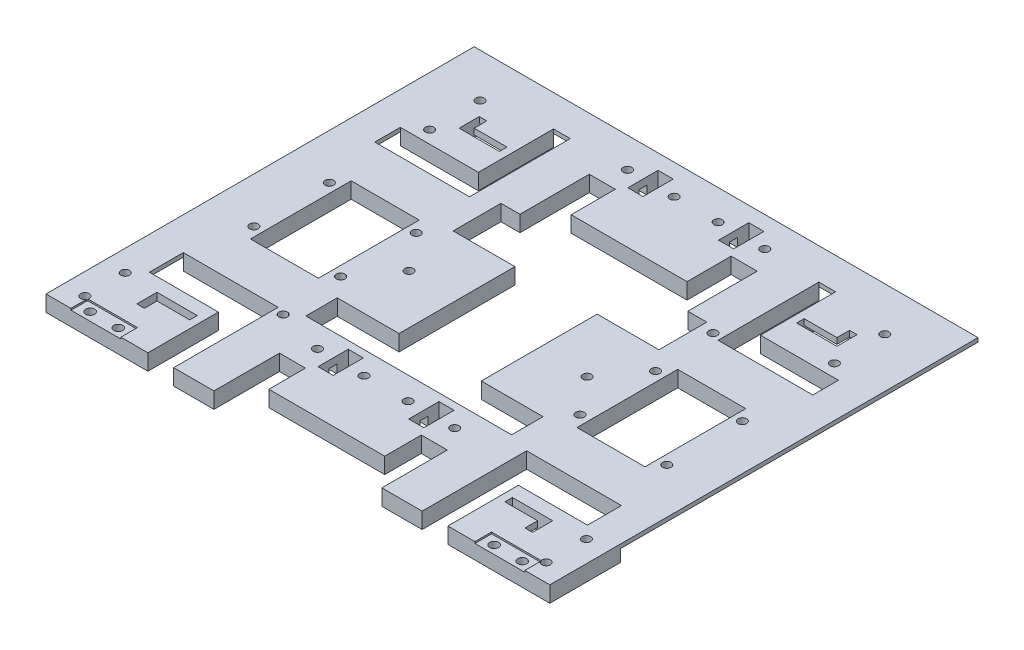
SolidWorks part; units mm, degrees
material "AISI 4130 Steel, normalized at 870C"
ref_plane "Front Plane" through (0, 0, 0) normal (0, 0, 1) x (1, 0, 0)
ref_plane "Top Plane" through (0, 0, 0) normal (0, 1, 0) x (1, 0, 0)
ref_plane "Right Plane" through (0, 0, 0) normal (1, 0, 0) x (0, 0, -1)
sketch "Sketch1" plane through (0, 0, 0) normal (0, 1, 0) x (1, 0, 0)
  line L1 (-100, -85) -> (100, -85)
  line L2 (-100, -85) -> (-100, 85)
  line L3 (-100, 85) -> (100, 85)
  line L4 (100, -85) -> (100, 85)
  line L5 (-100, -85) -> (100, 85) construction
  line L6 (-100, 85) -> (100, -85) construction
  point P0 (0, 0)
  dimension "D1" = 200
  dimension "D2" = 170
extrude "1/4\" Steel Plate" add sketch "Sketch1" along normal blind 6.35
ref_plane "Midplane" through (0, 0, 0) normal (-1, 0, 0) x (0, 0, 1)
sketch "Sketch2" plane through (0, 6.35, 0) normal (0, 1, 0) x (1, 0, 0)
  line L0 (-100, -85) -> (100, -85) construction
  line L1 (-90.094, -85) -> (-70.282, -85)
  line L2 (-90.094, -85) -> (-90.094, -78.396)
  line L3 (-90.094, -78.396) -> (-70.282, -78.396)
  line L4 (-70.282, -85) -> (-70.282, -78.396)
  line L5 (-100, 85) -> (-100, -85) construction
  dimension "D1" = 9.906
  dimension "D2" = 6.604
  dimension "D3" = 19.812
extrude "BladeHingeCut" cut sketch "Sketch2" against normal blind 0.635
hole_wizard "BladeHingeHole" positions "3DSketch2" profile "Sketch4" hole size "#8" standard "ANSI Inch" end condition through all
sketch3d "3DSketch2"
  line L0 (-90.094, 5.715, 85) -> (-70.282, 5.715, 85) construction
  line L10 (-80.188, 5.715, 78.396) -> (-80.188, 5.715, 85) construction
  line L11 (-70.282, 5.715, 78.396) -> (-90.094, 5.715, 78.396) construction
  point P0 (-74.6, 5.715, 81.698)
  point P2 (-85.776, 5.715, 81.698)
  dimension "D1" = 3.302
  dimension "D2" = 3.302
  dimension "D3" = 11.176
  dimension "D4" = 5.588
sketch "Sketch4" plane through (-74.6, 5.715, 81.698) normal (1, 0, 0) x (0, 0, 1)
  line L0 (0, 0) -> (0, 5.715)
  line L1 (0, 5.715) -> (1.778, 5.715)
  line L2 (1.778, 5.715) -> (1.778, 0)
  line L5 (1.778, 0) -> (0, 0)
  line L11 (0, -6.35) -> (0, 107.95) construction
  dimension "Thru Hole Dia." = 3.556
  dimension "Thru Hole Depth" = 5.715
sketch "Sketch5" plane through (0, 0, 0) normal (0, -1, 0) x (1, 0, 0)
  line L1 (-88.301, 79.173) -> (-83.251, 79.173)
  line L2 (-88.301, 79.173) -> (-88.301, 84.223)
  line L3 (-88.301, 84.223) -> (-83.251, 84.223)
  line L4 (-83.251, 79.173) -> (-83.251, 84.223)
  line L5 (-88.301, 79.173) -> (-83.251, 84.223) construction
  line L6 (-88.301, 84.223) -> (-83.251, 79.173) construction
  line L7 (-72.075, 79.173) -> (-77.125, 79.173)
  line L8 (-72.075, 79.173) -> (-72.075, 84.223)
  line L9 (-72.075, 84.223) -> (-77.125, 84.223)
  line L10 (-77.125, 79.173) -> (-77.125, 84.223)
  line L11 (-72.075, 79.173) -> (-77.125, 84.223) construction
  line L12 (-72.075, 84.223) -> (-77.125, 79.173) construction
  point P0 (-85.776, 81.698)
  point P6 (-74.6, 81.698)
  dimension "D1" = 5.05
  dimension "D2" = 5.05
  dimension "D3" = 5.05
  dimension "D4" = 5.05
extrude "BladeNutCut" cut sketch "Sketch5" against normal blind 2
mirror "BladeHingeMirror" about plane through (0, 0, 0) normal (-1, 0, 0) of "BladeNutCut", "BladeHingeHole", "BladeHingeCut"
sketch "Sketch6" plane through (0, 0, 0) normal (0, -1, 0) x (-1, 0, 0)
  line L0 (77.3259, -27.4233) -> (77.3259, 16.3767) construction
  line L1 (78.3259, 14.4767) -> (51.3259, 14.4767)
  line L2 (78.3259, 14.4767) -> (78.3259, -25.5233)
  line L3 (78.3259, -25.5233) -> (51.3259, -25.5233)
  line L4 (51.3259, 14.4767) -> (51.3259, -25.5233)
  line L5 (57.3259, 16.3767) -> (57.3259, -27.4233) construction
  point P6 (78.3259, -5.5233)
  dimension "D1" = 1
  dimension "D2" = 20
  dimension "D3" = 6
  dimension "D4" = 20
extrude "Cut-Extrude1" cut sketch "Sketch6" against normal up to surface (6.35 mm away) up to face at (0, 6.35, 54.4653)
sketch "Sketch7" plane through (0, 0, 0) normal (0, -1, 0) x (-1, 0, 0)
  line L0 (51.3259, -25.5233) -> (78.3259, -25.5233) construction
  line L1 (79.3259, -30.5233) -> (49.3259, -30.5233)
  line L2 (79.3259, -30.5233) -> (79.3259, -40.5233)
  line L3 (79.3259, -40.5233) -> (49.3259, -40.5233)
  line L4 (49.3259, -30.5233) -> (49.3259, -40.5233)
  line L5 (80.3259, 19.4767) -> (50.3259, 19.4767)
  line L6 (80.3259, 19.4767) -> (80.3259, 29.4767)
  line L7 (80.3259, 29.4767) -> (50.3259, 29.4767)
  line L8 (50.3259, 19.4767) -> (50.3259, 29.4767)
  line L9 (29.3259, -25.5233) -> (19.3259, -25.5233)
  line L10 (29.3259, -25.5233) -> (29.3259, 14.4767)
  line L11 (29.3259, 14.4767) -> (19.3259, 14.4767)
  line L12 (19.3259, -25.5233) -> (19.3259, 14.4767)
  line L17 (78.3259, -25.5233) -> (78.3259, 14.4767) construction
  line L18 (78.3259, 14.4767) -> (51.3259, 14.4767) construction
  line L19 (51.3259, 14.4767) -> (51.3259, -25.5233) construction
  line L29 (46.3259, -80.5233) -> (36.3259, -80.5233)
  line L30 (46.3259, -80.5233) -> (46.3259, -50.5233)
  line L31 (46.3259, -50.5233) -> (36.3259, -50.5233)
  line L32 (36.3259, -80.5233) -> (36.3259, -50.5233)
  line L33 (20, -70.5233) -> (-20, -70.5233)
  line L34 (20, -70.5233) -> (20, -60.5233)
  line L35 (20, -60.5233) -> (-20, -60.5233)
  line L36 (-20, -70.5233) -> (-20, -60.5233)
  line L37 (-100, 85) -> (100, 85) construction
  line L38 (36.3259, 39.4767) -> (46.3259, 39.4767)
  line L39 (36.3259, 39.4767) -> (36.3259, 69.4767)
  line L40 (36.3259, 69.4767) -> (46.3259, 69.4767)
  line L41 (46.3259, 39.4767) -> (46.3259, 69.4767)
  line L42 (20, 49.4767) -> (-20, 49.4767)
  line L43 (20, 49.4767) -> (20, 59.4767)
  line L44 (20, 59.4767) -> (-20, 59.4767)
  line L45 (-20, 49.4767) -> (-20, 59.4767)
  point P18 (0, 49.4767)
  point P55 (20, 54.4767)
  point P56 (36.3259, 54.4767)
  point P57 (20, -65.5233)
  point P58 (36.3259, -65.5233)
  point P60 (0, 85)
  dimension "D1" = 5
  dimension "D2" = 30
  dimension "D3" = 10
  dimension "D4" = 1
  dimension "D5" = 5
  dimension "D6" = 1
  dimension "D7" = 10
  dimension "D8" = 30
  dimension "D9" = 40
  dimension "D10" = 10
  dimension "D11" = 22
  dimension "D14" = 10
  dimension "D17" = 5
  dimension "D18" = 40
  dimension "D19" = 10
  dimension "D20" = 30
  dimension "D21" = 25
  dimension "D22" = 10
  dimension "D23" = 30
  dimension "D24" = 25
  dimension "D25" = 10
  dimension "D26" = 40
other "AlignGroup1"
extrude "Cut-Extrude2" cut sketch "Sketch7" against normal blind 5 contours L30 L29 L32 L31 | L34 L33 L36 L35 | L10 L9 L12 L11 | L2 L1 L4 L3 | L6 L5 L8 L7 | L39 L38 L41 L40 | L43 L42 L45 L44
sketch "Sketch8" plane through (0, 6.35, 0) normal (0, 1, 0) x (1, 0, 0)
  line L0 (-83.5459, -55) -> (-83.5459, -85) construction
  line L1 (-78.5459, -62.396) -> (-62.5459, -62.396)
  line L2 (-78.5459, -62.396) -> (-78.5459, -73.396)
  line L3 (-78.5459, -73.396) -> (-62.5459, -73.396)
  line L4 (-62.5459, -62.396) -> (-62.5459, -73.396)
  line L5 (-70.282, -78.396) -> (-90.094, -78.396) construction
  dimension "D1" = 11
  dimension "D2" = 16
  dimension "D3" = 5
  dimension "D4" = 5
extrude "Cut-Extrude3" cut sketch "Sketch8" along normal blind 4 from surface starting at face at (0, 0, -54.4767)
sketch "Sketch9" plane through (0, 4, 0) normal (0, -1, 0) x (1, 0, 0)
  line L0 (-78.5459, 62.396) -> (-62.5459, 62.396)
  line L9 (-78.5459, 62.396) -> (-78.5459, 70.396)
  line L10 (-78.5459, 73.396) -> (-78.5459, 62.396) construction
  line L11 (-78.5459, 70.396) -> (-75.5459, 70.396)
  line L12 (-75.5459, 70.396) -> (-75.5459, 65.396)
  line L13 (-75.5459, 65.396) -> (-62.5459, 65.396)
  line L14 (-62.5459, 62.396) -> (-62.5459, 73.396) construction
  line L15 (-62.5459, 65.396) -> (-62.5459, 62.396)
  dimension "D1" = 8
  dimension "D2" = 3
  dimension "D3" = 3
extrude "Cut-Extrude4" cut sketch "Sketch9" against normal up to surface (2.35 mm away) contours L13 L15 L0 L9 L11 L12 up to face at (-64.8259, 6.35, 5.5233)
sketch "Sketch10" plane through (0, 0, 0) normal (0, -1, 0) x (-1, 0, 0)
  line L1 (75, 65) -> (59, 65)
  line L2 (75, 65) -> (75, 54)
  line L3 (75, 54) -> (59, 54)
  line L4 (59, 65) -> (59, 54)
  line L6 (100, 85) -> (100, -85) construction
  line L7 (-100, 85) -> (100, 85) construction
  dimension "D1" = 11
  dimension "D2" = 16
  dimension "D3" = 25
  dimension "D4" = 20
extrude "Cut-Extrude5" cut sketch "Sketch10" against normal blind 4
sketch "Sketch11" plane through (0, 4, 0) normal (0, -1, 0) x (1, 0, 0)
  line L0 (-59, -54) -> (-75, -54)
  line L1 (-75, -54) -> (-75, -62)
  line L2 (-75, -54) -> (-75, -65) construction
  line L3 (-75, -62) -> (-72, -62)
  line L4 (-72, -62) -> (-72, -57)
  line L5 (-72, -57) -> (-59, -57)
  line L6 (-59, -65) -> (-59, -54) construction
  line L7 (-59, -57) -> (-59, -54)
  dimension "D1" = 3
  dimension "D2" = 3
  dimension "D3" = 8
extrude "Cut-Extrude6" cut sketch "Sketch11" against normal up to next
mirror "Mirror2" about plane through (0, 0, 0) normal (-1, 0, 0) of "Cut-Extrude6", "Cut-Extrude5", "Cut-Extrude4", "Cut-Extrude3", "Cut-Extrude2", "Cut-Extrude1"
hole_wizard "CSK for M3 Flat Head Machine Screw1" positions "Sketch12" profile "Sketch13" countersink size "M3" standard "ANSI Metric"
sketch "Sketch12" plane through (0, 0, 0) normal (0, -1, 0) x (-1, 0, 0)
  point P0 (-91.5503, -78)
  point P2 (-91.5503, -62)
  point P4 (-80.3371, 47.6378)
  point P7 (-80.3371, 67.6378)
  point P10 (-35.8509, -6.0466)
  point P13 (-45.8509, 33.9534)
  point P16 (35.8509, -5)
  point P19 (45.8509, -45)
  point P22 (91.5459, -62)
  point P25 (91.5459, -78)
  point P28 (80.3371, 47.6378)
  point P31 (80.3371, 67.6378)
  point P39 (-81.9659, -20.5233)
  point P42 (-81.9659, 9.4767)
  point P45 (-47.5109, -20.5233)
  point P48 (-47.5109, 9.4767)
  point P51 (47.5109, -20.5233)
  point P54 (81.9659, -20.5233)
  point P57 (81.9659, 9.4767)
  point P60 (47.5109, 9.4767)
sketch "Sketch13" plane through (91.5503, 0, 78) normal (1, 0, 0) x (0, 0, -1)
  line L0 (0, 0) -> (0, 14)
  line L1 (0, 14) -> (1.7, 14)
  line L2 (1.7, 14) -> (1.7, 1.45)
  line L3 (1.7, 1.45) -> (3.15, 0)
  line L5 (3.15, 0) -> (0, 0)
  line L6 (-1.7, 1.45) -> (-3.15, 0) construction
  line L10 (0, 14) -> (-1.7, 14) construction
  line L11 (0, -6.35) -> (0, 107.95) construction
  dimension "Hole Dia." = 3.4
  dimension "Hole Depth" = 14
  dimension "Near C'Sink Dia." = 6.3
  dimension "Near C'Sink Angle" = 90
  dimension "Drill Angle" = 180
sketch "Sketch14" plane through (0, 0, 0) normal (0, -1, 0) x (1, 0, 0)
  line L0 (0, -7.6262) -> (0, -14.6112) construction
  line L1 (21, 56) -> (15, 56)
  line L2 (21, 56) -> (21, 44)
  line L3 (21, 44) -> (15, 44)
  line L4 (15, 56) -> (15, 44)
  line L6 (-100, 85) -> (100, 85) construction
  point P6 (15, 50)
  dimension "D1" = 6
  dimension "D2" = 12
  dimension "D3" = 15
  dimension "D4" = 35
extrude "Cut-Extrude7" cut sketch "Sketch14" against normal blind 10
sketch "Sketch15" plane through (0, 0, 0) normal (0, -1, 0) x (1, 0, 0)
  line L1 (10.75, 48.4) -> (25.25, 48.4)
  line L2 (10.75, 48.4) -> (10.75, 51.6)
  line L3 (10.75, 51.6) -> (25.25, 51.6)
  line L4 (25.25, 48.4) -> (25.25, 51.6)
  line L5 (15, 56) -> (15, 44) construction
  line L6 (15, 44) -> (21, 44) construction
  point P6 (18, 44)
  point P9 (15, 50)
  point P10 (10.75, 50)
  point P11 (18, 48.4)
  dimension "D2" = 14.5
  dimension "D3" = 3.2
extrude "Cut-Extrude8" cut sketch "Sketch15" against normal blind 3.5
sketch "Sketch16" plane through (0, 0, 0) normal (0, -1, 0) x (1, 0, 0)
  line L0 (15, 44) -> (21, 44) construction
  line L1 (15, -79) -> (21, -79)
  line L2 (15, -79) -> (15, -67)
  line L3 (15, -67) -> (21, -67)
  line L4 (21, -79) -> (21, -67)
  line L5 (100, -85) -> (-100, -85) construction
  point P6 (18, 44)
  point P7 (18, -67)
  point P8 (15, -73)
  dimension "D1" = 12
  dimension "D2" = 6
  dimension "D3" = 12
extrude "Cut-Extrude9" cut sketch "Sketch16" against normal through all
sketch "Sketch17" plane through (0, 0, 0) normal (0, -1, 0) x (1, 0, 0)
  line L1 (10.75, -74.6) -> (25.25, -74.6)
  line L2 (10.75, -74.6) -> (10.75, -71.4)
  line L3 (10.75, -71.4) -> (25.25, -71.4)
  line L4 (25.25, -74.6) -> (25.25, -71.4)
  line L8 (21, -67) -> (15, -67) construction
  line L9 (15, -67) -> (15, -79) construction
  point P6 (15, -73)
  point P7 (10.75, -73)
  point P14 (18, -67)
  point P15 (18, -71.4)
  dimension "D1" = 14.5
  dimension "D2" = 3.2
extrude "Cut-Extrude10" cut sketch "Sketch17" against normal blind 3.5
hole_wizard "CSK for M3 Flat Head Machine Screw2" positions "Sketch18" profile "Sketch19" countersink size "M3" standard "ANSI Metric"
sketch "Sketch18" plane through (0, 0, 0) normal (0, -1, 0) x (-1, 0, 0)
  line L2 (-21, 74.6) -> (-25.25, 74.6) construction
  line L4 (-10.75, 74.6) -> (-15, 74.6) construction
  line L5 (-25.25, 74.6) -> (-25.25, 71.4) construction
  line L6 (-10.75, 71.4) -> (-10.75, 74.6) construction
  line L7 (-25.25, -48.4) -> (-25.25, -51.6) construction
  point P0 (-8.75, -50)
  point P4 (-27.25, -50)
  point P6 (-8.75, 73.1)
  point P8 (-27.25, 73.1)
  point P27 (0, 0)
  point P30 (-25.25, -50)
  dimension "D1" = 1.5
  dimension "D2" = 1.5
  dimension "D3" = 2
  dimension "D4" = 2
sketch "Sketch19" plane through (8.75, 0, 50) normal (1, 0, 0) x (0, 0, -1)
  line L0 (0, 0) -> (0, 11.0215)
  line L1 (0, 11.0215) -> (1.7, 10)
  line L2 (1.7, 10) -> (1.7, 1.45)
  line L3 (1.7, 1.45) -> (3.15, 0)
  line L5 (3.15, 0) -> (0, 0)
  line L6 (-1.7, 1.45) -> (-3.15, 0) construction
  line L10 (0, 11.0215) -> (-1.7, 10) construction
  line L11 (0, -6.35) -> (0, 107.95) construction
  dimension "Hole Dia." = 3.4
  dimension "Hole Depth" = 10
  dimension "Near C'Sink Dia." = 6.3
  dimension "Near C'Sink Angle" = 90
  dimension "Drill Angle" = 118
mirror "Mirror3" about plane through (0, 0, 0) normal (-1, 0, 0) of "Cut-Extrude7", "Cut-Extrude8", "Cut-Extrude9", "Cut-Extrude10", "CSK for M3 Flat Head Machine Screw2"
sketch "Sketch20" plane through (0, 0, 0) normal (0, -1, 0) x (1, 0, 0)
  line L0 (-100, 85) -> (100, 85) construction
  line L1 (-59.5459, 85) -> (-49.3259, 85)
  line L2 (-59.5459, 85) -> (-59.5459, 57)
  line L3 (-50.8509, 50) -> (-49.3259, 50)
  line L4 (-49.3259, 85) -> (-49.3259, 50)
  line L5 (-100, -85) -> (-100, 85) construction
  line L6 (-100, 57) -> (-59.5459, 57)
  line L7 (-100, 57) -> (-100, 45.2891)
  line L8 (-86.9659, 43.5233) -> (-50.8509, 43.5233)
  line L9 (-50.8509, 50) -> (-50.8509, 43.5233)
  line L10 (100, -85) -> (-100, -85) construction
  line L12 (-86.9659, 43.5233) -> (-86.9659, -32.4767)
  line L13 (-89.1269, -85) -> (-100, -85)
  line L14 (-100, 45.2891) -> (-100, -85)
  line L15 (-86.9659, -32.4767) -> (-49.3259, -32.4767)
  line L17 (-86.9659, -42.6378) -> (-56, -42.6378)
  line L18 (-49.3259, -35.2903) -> (-49.3259, -42.3731)
  line L19 (-86.9659, -72.4767) -> (-56, -72.4767)
  line L21 (-89.1269, -85) -> (-46.8803, -85)
  line L23 (-86.9659, -42.6378) -> (-86.9659, -72.4767)
  line L25 (-56, -42.6378) -> (-56, -72.4767)
  line L27 (-49.3259, -42.3731) -> (-49.3259, -72.4767)
  line L28 (-40.8509, -17.4767) -> (-20.1564, -17.4767)
  line L29 (-40.8509, -17.4767) -> (-40.8509, -31.3828)
  line L30 (-40.8509, -36.4767) -> (-33.3259, -36.4767)
  line L33 (-33.3259, -36.4767) -> (-33.3259, -64)
  line L34 (-33.3259, -64) -> (-23, -64)
  line L35 (-23, -46.4767) -> (-23, -64)
  line L36 (-44.7194, -72.4767) -> (-32.25, -72.4767)
  line L38 (-46.8803, -85) -> (-32.25, -85)
  line L39 (-32.25, -72.4767) -> (-32.25, -85)
  line L40 (-40.8509, 41) -> (-20.1564, 41)
  line L41 (-40.8509, 41) -> (-40.8509, 28.5233)
  line L42 (-40.8509, 28.5233) -> (-20.1564, 28.5233)
  line L44 (-33.3259, 85) -> (-23, 85)
  line L45 (-33.3259, 85) -> (-33.3259, 59)
  line L46 (-33.3259, 59) -> (-23, 59)
  line L47 (-23, 85) -> (-23, 59)
  line L48 (0, 41) -> (-15.9718, 41)
  line L49 (0, 41) -> (0, -46.4767)
  line L50 (0, -46.4767) -> (-15.9718, -46.4767)
  line L51 (-16.3259, 28.5233) -> (-16.3259, -17.4767)
  line L52 (-49.3259, -72.4767) -> (-44.7194, -72.4767)
  line L54 (-40.8509, -31.3828) -> (-40.8509, -36.4767)
  line L55 (-20.1564, 41) -> (-15.9718, 41)
  line L57 (-20.1564, 28.5233) -> (-16.3259, 28.5233)
  line L59 (-20.1564, -17.4767) -> (-16.3259, -17.4767)
  line L61 (-20.1564, -46.4767) -> (-15.9718, -46.4767)
  line L65 (-23, -46.4767) -> (-20.1564, -46.4767)
  line L71 (-49.3259, -32.4767) -> (-49.3259, -35.2903)
  line L72 (-46.3259, -39.4767) -> (-46.3259, -69.4767) construction
  line L73 (-80.3259, -29.4767) -> (-50.3259, -29.4767) construction
  line L74 (-79.3259, 40.5233) -> (-49.3259, 40.5233) construction
  line L75 (-46.3259, 80.5233) -> (-46.3259, 50.5233) construction
  line L76 (-62.5459, 65.396) -> (-62.5459, 73.396) construction
  line L77 (-36.3259, 80.5233) -> (-36.3259, 50.5233) construction
  line L78 (-20, 70.5233) -> (-20, 60.5233) construction
  line L79 (-21, 56) -> (-15, 56) construction
  line L80 (-15, 44) -> (-21, 44) construction
  line L81 (-29.3259, 25.5233) -> (-19.3259, 25.5233) construction
  line L82 (-19.3259, 25.5233) -> (-19.3259, -14.4767) construction
  line L83 (-29.3259, -14.4767) -> (-19.3259, -14.4767) construction
  line L84 (-20, -49.4767) -> (20, -49.4767) construction
  line L85 (-20, -49.4767) -> (-20, -59.4767) construction
  line L86 (-36.3259, -39.4767) -> (-36.3259, -69.4767) construction
  line L87 (-36.3259, -39.4767) -> (-46.3259, -39.4767) construction
  line L88 (-21, -67) -> (-15, -67) construction
  line L89 (-36.3259, -69.4767) -> (-46.3259, -69.4767) construction
  line L90 (-59, -65) -> (-59, -54) construction
  line L91 (0, 3.4925) -> (0, -3.4925) construction
  line L92 (-20, 70.5233) -> (20, 70.5233) construction
  line L93 (-23, 85) -> (0, 85)
  line L94 (-23, 85) -> (-23, 73.5233)
  line L95 (-23, 73.5233) -> (0, 73.5233)
  line L96 (0, 85) -> (0, 73.5233)
  circle A0 centre (-45.8509, 45) radius 1.7 construction
  circle A1 centre (-81.9659, 20.5233) radius 1.7 construction
  circle A2 centre (-91.5459, 62) radius 1.7 construction
  circle A3 centre (-27.25, -73.1) radius 1.7 construction
  circle A4 centre (-80.3371, -47.6378) radius 1.7 construction
  dimension "D1" = 5
  dimension "D10" = 5
  dimension "D2" = 3
  dimension "D3" = 3
  dimension "D4" = 5
  dimension "D5" = 3
  dimension "D6" = 5
  dimension "D7" = 5
  dimension "D8" = 3
  dimension "D9" = 3
  dimension "D11" = 3
  dimension "D12" = 3
  dimension "D13" = 3
  dimension "D14" = 3
  dimension "D15" = 3
  dimension "D16" = 5
  dimension "D17" = 3
  dimension "D18" = 3
  dimension "D19" = 3
  dimension "D20" = 3
  dimension "D21" = 3
  dimension "D22" = 3
  dimension "D23" = 3
  dimension "D24" = 3
  dimension "D25" = 5
  dimension "D26" = 5
  dimension "D27" = 3
  dimension "D28" = 3
extrude "Cut-Extrude11" cut sketch "Sketch20" against normal blind 4.7625 contours L47 L44 L45 L46 | L35 L65 L61 L50 L49 L48 L55 L40 L41 L42 L57 L51 L59 L28 L29 L54 L30 L33 L34 | L71 L15 L12 L8 L9 L3 L4 L1 L2 L6 L7 L14 L13 L21 L38 L39 L36 L52 L27 L18 L17 L25 L19 L23 | L94 L93 L96 L95 region at (-54.4359, 0, 83.17) region at (-30.5037, 0, -18.6034) region at (-28.163, 0, 72)
mirror "Mirror4" about plane through (0, 0, 0) normal (-1, 0, 0) of "Cut-Extrude11"
sketch "Sketch21" plane through (0, 0, 0) normal (0, -1, 0) x (1, 0, 0)
  line L0 (40.8509, -17.4767) -> (16.3259, -17.4767) construction
  line L1 (-40.8509, 41) -> (40.8509, 41)
  line L2 (-40.8509, 41) -> (-40.8509, 28.5233)
  line L3 (-40.8509, 28.5233) -> (-16.3259, 28.5233)
  line L4 (40.8509, 41) -> (40.8509, 28.5233)
  line L6 (-16.3259, 28.5233) -> (-16.3259, -17.4767)
  line L8 (16.3259, 28.5233) -> (16.3259, -17.4767)
  line L9 (-23, -46.4767) -> (23, -46.4767)
  line L11 (-28.5884, -17.4767) -> (-16.3259, -17.4767)
  line L13 (-59.5459, 85) -> (-59.5459, 57) construction
  line L14 (-33.3259, -64) -> (-23, -64)
  line L15 (-33.3259, -64) -> (-33.3259, -36.4767)
  line L16 (-33.3259, -17.4767) -> (-28.5884, -17.4767)
  line L17 (-23, -64) -> (-23, -46.4767)
  line L18 (33.3259, -64) -> (23, -64)
  line L19 (33.3259, -64) -> (33.3259, -36.4767)
  line L20 (28.5884, -17.4767) -> (21.5374, -17.4767)
  line L21 (23, -64) -> (23, -46.4767)
  line L22 (-40.8509, -17.4767) -> (-16.3259, -17.4767)
  line L23 (-40.8509, -17.4767) -> (-40.8509, -36.4767)
  line L24 (-40.8509, -36.4767) -> (-33.3259, -36.4767)
  line L25 (40.8509, -17.4767) -> (40.8509, -36.4767)
  line L26 (-49.3259, -32.4767) -> (-86.9659, -32.4767)
  line L27 (-49.3259, -32.4767) -> (-49.3259, -42.6378)
  line L28 (-56, -42.6378) -> (-86.9659, -42.6378)
  line L29 (-86.9659, -32.4767) -> (-86.9659, -42.6378)
  line L30 (86.9659, -42.6378) -> (56, -42.6378)
  line L31 (86.9659, -42.6378) -> (86.9659, -32.4767)
  line L32 (86.9659, -32.4767) -> (49.3259, -32.4767)
  line L33 (49.3259, -42.6378) -> (49.3259, -32.4767)
  line L34 (-86.9659, 43.5233) -> (-59.5459, 43.5233)
  line L35 (-86.9659, 43.5233) -> (-86.9659, 57)
  line L36 (-86.9659, 57) -> (-59.5459, 57)
  line L38 (16.3259, 28.5233) -> (40.8509, 28.5233)
  line L39 (59.5459, 57) -> (86.9659, 57)
  line L41 (59.5459, 43.5233) -> (86.9659, 43.5233)
  line L42 (86.9659, 57) -> (86.9659, 43.5233)
  line L43 (16.3259, -17.4767) -> (21.5374, -17.4767)
  line L44 (16.3259, -17.4767) -> (40.8509, -17.4767)
  line L45 (33.3259, -36.4767) -> (40.8509, -36.4767)
  line L46 (23, -46.4767) -> (23, -64) construction
  line L48 (-100, 57) -> (-59.5459, 57) construction
  line L49 (-33.3259, 85) -> (33.3259, 85) construction
  line L50 (-49.3259, -72.4767) -> (-56, -72.4767)
  line L51 (-49.3259, -72.4767) -> (-49.3259, -42.6378)
  line L53 (-56, -72.4767) -> (-56, -42.6378)
  line L55 (49.3259, -42.6378) -> (49.3259, -72.4767)
  line L56 (49.3259, -72.4767) -> (56, -72.4767)
  line L57 (56, -42.6378) -> (56, -72.4767)
  line L58 (-33.3259, 59) -> (-23, 59)
  line L59 (-33.3259, 59) -> (-33.3259, 85)
  line L60 (-33.3259, 85) -> (-23, 85)
  line L61 (-23, 59) -> (-23, 73.5233)
  line L62 (-23, 73.5233) -> (-23, 59) construction
  line L63 (-23, 85) -> (23, 85)
  line L65 (-23, 73.5233) -> (23, 73.5233)
  line L67 (33.3259, 85) -> (23, 85)
  line L68 (33.3259, 85) -> (33.3259, 59)
  line L69 (33.3259, 59) -> (23, 59)
  line L70 (23, 73.5233) -> (23, 59)
  line L71 (49.3259, 85) -> (59.5459, 85)
  line L72 (49.3259, 85) -> (49.3259, 43.5233)
  line L73 (49.3259, 43.5233) -> (59.5459, 43.5233)
  line L74 (59.5459, 85) -> (59.5459, 57)
  line L75 (-49.3259, 85) -> (-59.5459, 85)
  line L76 (-49.3259, 85) -> (-49.3259, 43.5233)
  line L77 (-49.3259, 43.5233) -> (-59.5459, 43.5233)
  line L78 (-59.5459, 85) -> (-59.5459, 57)
extrude "Cut-Extrude12" cut sketch "Sketch21" against normal up to surface (6.35 mm away) contours L14 L17 L16 L15 | L9 L11 | L21 L18 L19 L20 | L8 L3 L6 | L4 L1 L2 L3 | L65 L70 L69 L68 L67 L63 L60 L59 L58 L61 | L15 L14 L17 L16 | L23 L22 L25 L24 | L31 L32 L33 L55 L56 L57 L30 | L39 L42 L41 L73 L72 L71 L74 | L35 L36 L78 L75 L76 L77 L34 | L27 L51 L50 L53 L28 L29 L26 region at (0, 0, -8.973) region at (0, 0, 75.6001) up to face at (-8.75, 6.35, 48.3)
